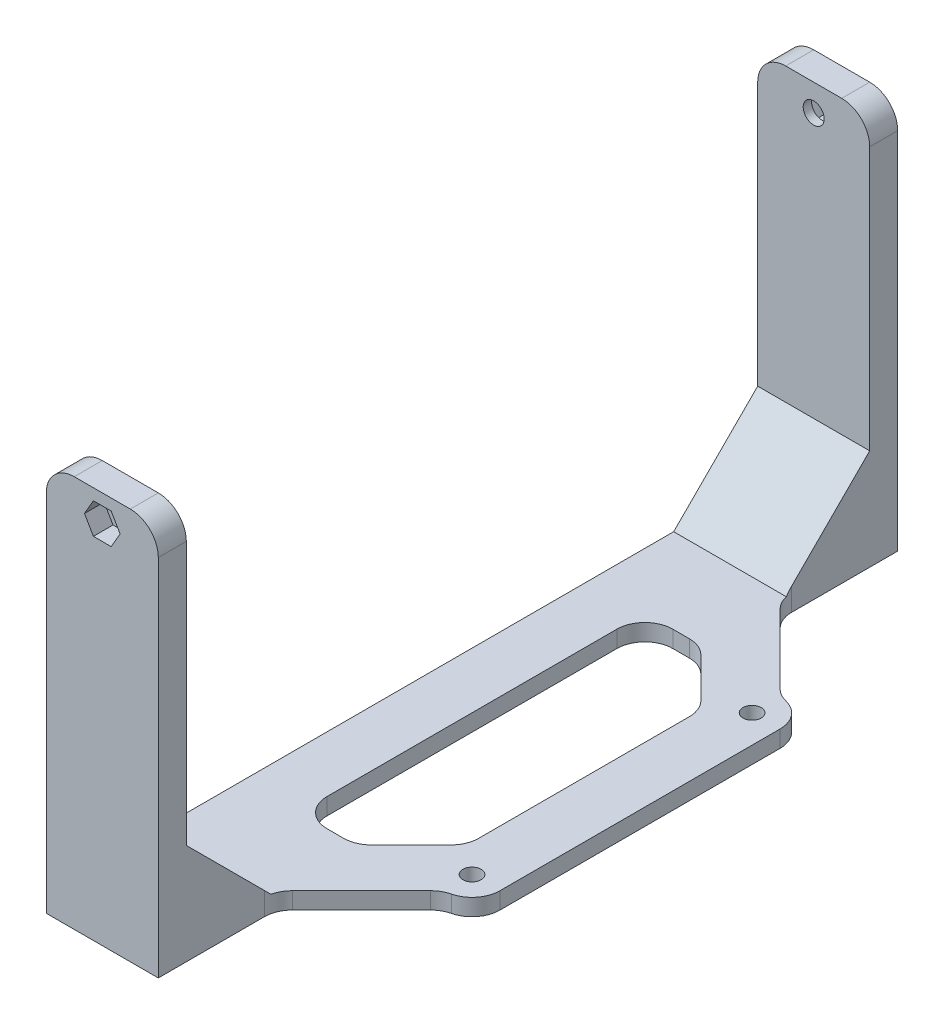
SolidWorks part; units mm, degrees
ref_plane "Front Plane" through (0, 0, 0) normal (0, 0, 1) x (1, 0, 0)
ref_plane "Top Plane" through (0, 0, 0) normal (0, 1, 0) x (1, 0, 0)
ref_plane "Right Plane" through (0, 0, 0) normal (1, 0, 0) x (0, 0, -1)
sketch "Sketch1" plane through (0, 0, 0) normal (0, 1, 0) x (1, 0, 0)
  line L1 (-10, -66) -> (10, -66)
  line L2 (-10, -66) -> (-10, 66)
  line L3 (-10, 66) -> (10, 66)
  line L4 (10, -66) -> (10, 66)
  line L5 (-10, -66) -> (10, 66) construction
  line L6 (-10, 66) -> (10, -66) construction
  point P0 (0, 0)
  dimension "D1" = 132
  dimension "D2" = 20
extrude "Boss-Extrude1" add sketch "Sketch1" along normal blind 3
sketch "Sketch2" plane through (0, 3, 0) normal (0, 1, 0) x (1, 0, 0)
  line L0 (10, -66) -> (10, 66) construction
  line L1 (-10, -66) -> (10, -66)
  line L2 (-10, -66) -> (-10, -61)
  line L3 (-10, -61) -> (10, -61)
  line L4 (10, -66) -> (10, -61)
  line L6 (-10, 66) -> (10, 66)
  line L7 (-10, 66) -> (-10, 61)
  line L8 (-10, 61) -> (10, 61)
  line L9 (10, 66) -> (10, 61)
  dimension "D1" = 5
  dimension "D2" = 5
extrude "Boss-Extrude2" add sketch "Sketch2" along normal blind 67
sketch "Sketch4" plane through (0, 0, 66) normal (0, 0, 1) x (1, 0, 0)
  line L0 (-10, 65.2375) -> (10, 65.2375) construction
  line L1 (-10, 70) -> (-10, 0) construction
  line L2 (10, 70) -> (10, 0) construction
  line L3 (-10, 70) -> (10, 70) construction
  circle A0 centre (0, 65.2375) radius 1.875
  dimension "D1" = 3.75
  dimension "D2" = 4.7625
extrude "Cut-Extrude1" cut sketch "Sketch4" against normal through all
fillet "Fillet3" radius 5 4 edges at (10, 70, 63.5) (-10, 70, 63.5) (10, 70, -63.5) (-10, 70, -63.5)
sketch "Sketch6" plane through (0, 0, 66) normal (0, 0, 1) x (1, 0, 0)
  line L1 (3.1754, 65.2375) -> (1.5877, 67.9875)
  line L2 (1.5877, 67.9875) -> (-1.5877, 67.9875)
  line L3 (-1.5877, 67.9875) -> (-3.1754, 65.2375)
  line L4 (-3.1754, 65.2375) -> (-1.5877, 62.4875)
  line L5 (-1.5877, 62.4875) -> (1.5877, 62.4875)
  line L6 (1.5877, 62.4875) -> (3.1754, 65.2375)
  circle A0 centre (0, 65.2375) radius 2.75 construction
  dimension "D1" = 5.5
extrude "Cut-Extrude2" cut sketch "Sketch6" against normal blind 3.5
sketch "Sketch7" plane through (0, 0, -66) normal (0, 0, -1) x (-1, 0, 0)
  line L1 (3.2043, 65.2375) -> (1.6021, 68.0125)
  line L2 (1.6021, 68.0125) -> (-1.6021, 68.0125)
  line L3 (-1.6021, 68.0125) -> (-3.2043, 65.2375)
  line L4 (-3.2043, 65.2375) -> (-1.6021, 62.4625)
  line L5 (-1.6021, 62.4625) -> (1.6021, 62.4625)
  line L6 (1.6021, 62.4625) -> (3.2043, 65.2375)
  circle A0 centre (0, 65.2375) radius 2.775 construction
  dimension "D1" = 5.55
extrude "Cut-Extrude3" cut sketch "Sketch7" against normal blind 3.5
sketch "Sketch9" plane through (0, 0, 0) normal (0, -1, 0) x (1, 0, 0)
  line L0 (0, 0) -> (50000, 0) construction
  line L1 (10, 66) -> (10, -66) construction
  line L2 (30, -30) -> (10, -30)
  line L3 (30, -30) -> (30, 30)
  line L4 (30, 30) -> (10, 30)
  line L5 (10, -30) -> (10, 30)
  line L6 (30, -30) -> (10, 30) construction
  line L7 (30, 30) -> (10, -30) construction
  line L8 (25, -25) -> (25, 25) construction
  circle A0 centre (25, -25) radius 1.625
  circle A1 centre (25, 25) radius 1.625
  point P3 (20, 0)
  point P13 (25, 0)
  dimension "D2" = 3.25
  dimension "D1" = 50
  dimension "D3" = 5
  dimension "D4" = 5
  dimension "D5" = 20
extrude "Boss-Extrude3" add sketch "Sketch9" against normal up to surface (3 mm away) up to face at (0, 3, 0)
chamfer "Chamfer1" distance 15 angle 45 4 edges at (0, 3, 61) (0, 3, -61) (10, 1.5, 30) (10, 1.5, -30)
fillet "Fillet4" radius 5 2 edges at (30, 1.5, 30) (30, 1.5, -30)
sketch "Sketch10" plane through (0, 3, 0) normal (0, 1, 0) x (1, 0, 0)
  line L0 (0, 0) -> (50000, 0) construction
  line L1 (0, 30.8579) -> (0, -30.8579)
  line L2 (0, -30.8579) -> (10, -30.8579)
  line L3 (10, -30.8579) -> (20, -20.8579)
  line L4 (20, -20.8579) -> (20, 20.8579)
  line L5 (20, 20.8579) -> (10, 30.8579)
  line L6 (10, 30.8579) -> (0, 30.8579)
  line L7 (25, 30) -> (10, 45) construction
  line L8 (30, -25) -> (30, 25) construction
  line L9 (10, -45) -> (25, -30) construction
  point P6 (0, 0)
  point P14 (34.4645, -13.4644)
  point P15 (0, -30.6281)
  point P16 (33.2179, -7.64)
  point P17 (29.8528, -11.0051)
  dimension "D1" = 10
  dimension "D2" = 10
  dimension "D3" = 10
extrude "Cut-Extrude4" cut sketch "Sketch10" against normal through all
fillet "Fillet5" radius 5 10 edges at (20, 1.5, 20.8579) (20, 1.5, -20.8579) (10, 1.5, -30.8579) (0, 1.5, -30.8579) (0, 1.5, 30.8579) (10, 1.5, 30.8579) (10, 1.5, 45) (10, 1.5, -45) (25, 1.5, 30) (25, 1.5, -30)
